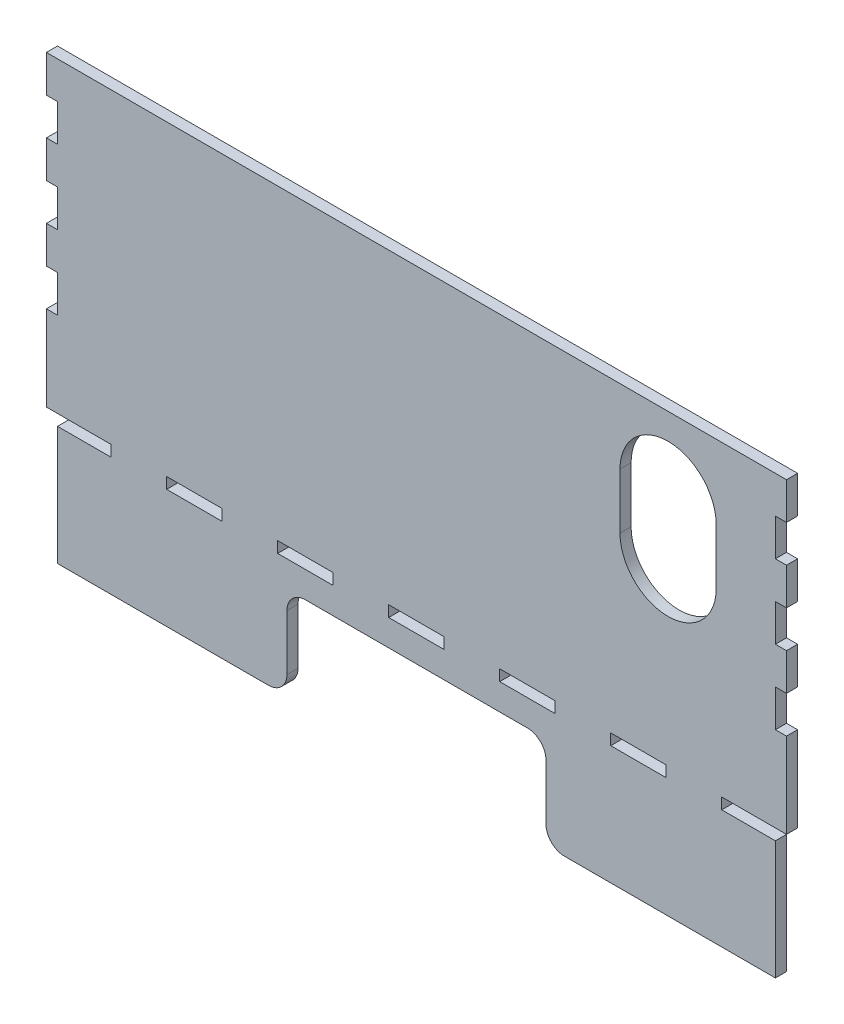
SolidWorks part; units mm, degrees
ref_plane "Front Plane" through (0, 0, 0) normal (0, 0, 1) x (1, 0, 0)
ref_plane "Top Plane" through (0, 0, 0) normal (0, 1, 0) x (1, 0, 0)
ref_plane "Right Plane" through (0, 0, 0) normal (1, 0, 0) x (0, 0, -1)
sketch "Sketch1" plane through (0, 0, 0) normal (0, 0, 1) x (1, 0, 0)
  line L0 (-97, 0) -> (97, 0) construction
  line L1 (0, -25.5) -> (0, 57.5) construction
  line L2 (100, -2.5) -> (97, -2.5)
  line L3 (-97, 57.5) -> (97, 57.5)
  line L4 (100, -25.5) -> (100, -2.5)
  line L5 (0, -25.5) -> (7.5, -25.5)
  line L6 (-97, -25.5) -> (-100, -25.5)
  line L7 (-100, -25.5) -> (-100, -2.5)
  line L8 (-97, 57.5) -> (-100, 57.5)
  line L9 (-100, 57.5) -> (-100, 47.5)
  line L10 (-100, 47.5) -> (-97, 47.5)
  line L11 (-97, 47.5) -> (-97, 37.5)
  line L12 (-97, 37.5) -> (-100, 37.5)
  line L13 (-100, 37.5) -> (-100, 27.5)
  line L14 (100, 17.5) -> (100, 7.5)
  line L15 (-100, 27.5) -> (-97, 27.5)
  line L16 (-97, 27.5) -> (-97, 17.5)
  line L17 (97, 7.5) -> (100, 7.5)
  line L18 (97, 17.5) -> (100, 17.5)
  line L19 (97, 7.5) -> (97, -2.5)
  line L20 (97, 27.5) -> (97, 17.5)
  line L21 (100, 27.5) -> (97, 27.5)
  line L22 (100, 37.5) -> (100, 27.5)
  line L23 (97, 37.5) -> (100, 37.5)
  line L24 (97, 47.5) -> (97, 37.5)
  line L25 (100, 47.5) -> (97, 47.5)
  line L26 (100, 57.5) -> (100, 47.5)
  line L27 (97, 57.5) -> (100, 57.5)
  line L28 (7.5, -25.5) -> (7.5, -28.5)
  line L29 (7.5, -28.5) -> (22.5, -28.5)
  line L30 (22.5, -28.5) -> (22.5, -25.5)
  line L31 (30, -25.5) -> (37.5, -25.5)
  line L32 (37.5, -25.5) -> (37.5, -28.5)
  line L33 (37.5, -28.5) -> (52.5, -28.5)
  line L34 (52.5, -28.5) -> (52.5, -25.5)
  line L35 (60, -25.5) -> (67.5, -25.5)
  line L36 (67.5, -25.5) -> (67.5, -28.5)
  line L37 (67.5, -28.5) -> (82.5, -28.5)
  line L38 (82.5, -28.5) -> (82.5, -25.5)
  line L39 (22.5, -25.5) -> (30, -25.5)
  line L40 (52.5, -25.5) -> (60, -25.5)
  line L41 (82.5, -25.5) -> (97, -25.5)
  line L42 (0, -25.5) -> (-7.5, -25.5)
  line L43 (-7.5, -25.5) -> (-7.5, -28.5)
  line L44 (-7.5, -28.5) -> (-22.5, -28.5)
  line L45 (-22.5, -28.5) -> (-22.5, -25.5)
  line L46 (-22.5, -25.5) -> (-37.5, -25.5)
  line L47 (-37.5, -25.5) -> (-37.5, -28.5)
  line L48 (-37.5, -28.5) -> (-52.5, -28.5)
  line L49 (-52.5, -28.5) -> (-52.5, -25.5)
  line L50 (-52.5, -25.5) -> (-67.5, -25.5)
  line L51 (-67.5, -25.5) -> (-67.5, -28.5)
  line L52 (-100, -2.5) -> (-97, -2.5)
  line L53 (97, -25.5) -> (100, -25.5)
  line L56 (-97, 7.5) -> (-97, -2.5)
  line L57 (-97, 17.5) -> (-100, 17.5)
  line L58 (-97, 7.5) -> (-100, 7.5)
  line L59 (-100, 17.5) -> (-100, 7.5)
  line L60 (-67.5, -28.5) -> (-82.5, -28.5)
  line L62 (-82.5, -28.5) -> (-82.5, -25.5)
  line L63 (-82.5, -25.5) -> (-97, -25.5)
  dimension "D2" = 7.5
  dimension "D4" = 83
  dimension "D5" = 10
  dimension "D6" = 194
  dimension "D8" = 7.5
  dimension "D9" = 15
  dimension "D10" = 3
  dimension "D11" = 10
  dimension "D7" = 10
  dimension "D13" = 10
  dimension "D12" = 10
  dimension "D14" = 7.5
  dimension "D15" = 14.5
  dimension "D16" = 10
  dimension "D18" = 3
  dimension "D19" = 15
  dimension "D20" = 15
  dimension "D21" = 15
  dimension "D22" = 15
  dimension "D23" = 15
extrude "Boss-Extrude1" add sketch "Sketch1" along normal blind 3
sketch "Sketch2" plane through (0, 0, 3) normal (0, 0, 1) x (1, 0, 0)
  line L0 (0, -25.5) -> (0, 22.5) construction
  line L1 (-7.5, -25.5) -> (7.5, -25.5) construction
  line L2 (0, 22.5) -> (68, 22.5) construction
  line L3 (68, 22.5) -> (68, 37.5) construction
  line L4 (55, 22.5) -> (55, 37.5)
  line L5 (81, 22.5) -> (81, 37.5)
  arc A0 (55, 22.5) -> (81, 22.5) centre (68, 22.5) ccw
  arc A1 (81, 37.5) -> (55, 37.5) centre (68, 37.5) ccw
  point P7 (68, 30)
  dimension "D4" = 13
  dimension "D1" = 48
  dimension "D2" = 68
  dimension "D3" = 15
extrude "Cut-Extrude1" cut sketch "Sketch2" against normal blind 10
sketch "Sketch3" plane through (0, -28.5, 0) normal (0, -1, 0) x (1, 0, 0)
  line L0 (-100, 3) -> (-82.5, 3) construction
  line L1 (-97, 3) -> (97, 3)
  line L2 (-97, 3) -> (-97, 0)
  line L3 (-97, 0) -> (97, 0)
  line L4 (97, 3) -> (97, 0)
  line L5 (82.5, 0) -> (100, 0) construction
  line L6 (-100, 3) -> (-100, 0) construction
  line L7 (100, 3) -> (100, 0) construction
  point P8 (-100, 1.5)
  point P11 (100, 1.5)
  dimension "D1" = 3
  dimension "D2" = 3
extrude "Boss-Extrude2" add sketch "Sketch3" along normal blind 32.11
sketch "Sketch4" plane through (0, 0, 3) normal (0, 0, 1) x (1, 0, 0)
  line L0 (0, -60.61) -> (0, -46.61) construction
  line L1 (97, -60.61) -> (-97, -60.61) construction
  line L3 (-35, -35.61) -> (35, -35.61)
  line L4 (-35, -35.61) -> (-35, -60.61)
  line L5 (-35, -60.61) -> (35, -60.61)
  line L6 (35, -35.61) -> (35, -60.61)
  dimension "D1" = 14
  dimension "D2" = 70
  dimension "D3" = 25
  dimension "D4" = 35
extrude "Cut-Extrude2" cut sketch "Sketch4" against normal blind 22
fillet "Fillet1" radius 5 2 edges at (35, -60.61, 1.5) (-35, -60.61, 1.5)
fillet "Fillet2" radius 5 2 edges at (35, -35.61, 1.5) (-35, -35.61, 1.5)
